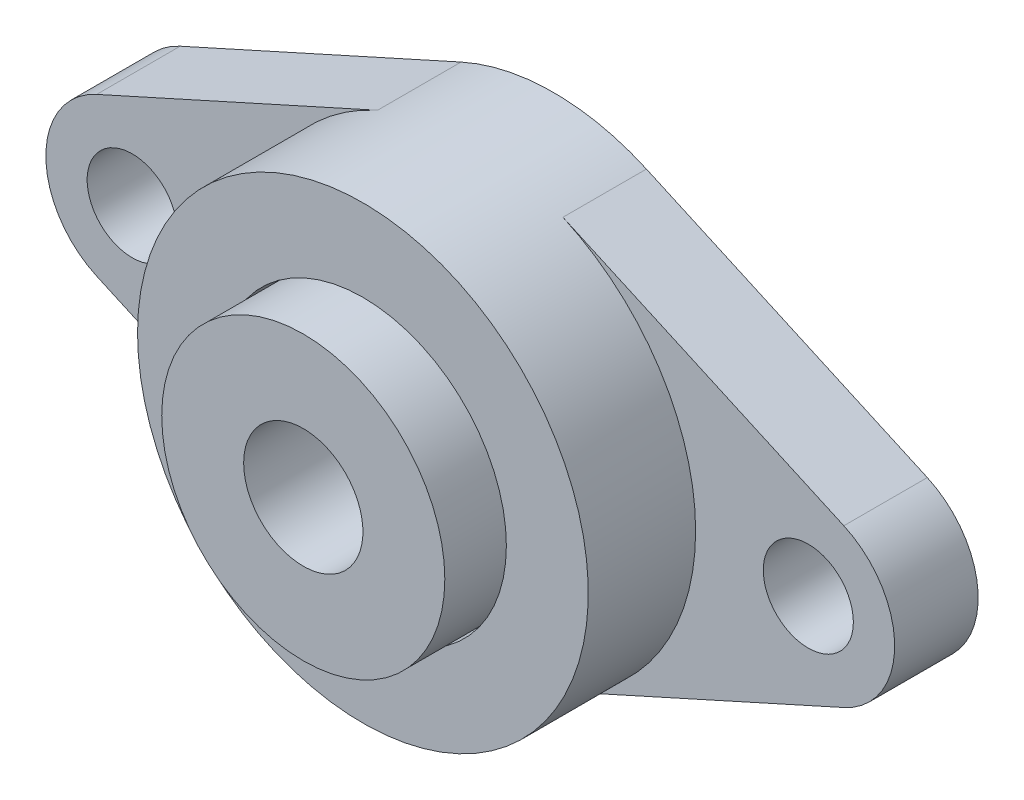
SolidWorks part; units mm, degrees
material "Cast Alloy Steel"
ref_plane "Front" through (0, 0, 0) normal (0, 0, 1) x (1, 0, 0)
ref_plane "Top" through (0, 0, 0) normal (0, 1, 0) x (1, 0, 0)
ref_plane "Right" through (0, 0, 0) normal (1, 0, 0) x (0, 0, -1)
sketch "Sketch1" plane through (0, 0, 0) normal (0, 0, 1) x (1, 0, 0)
  line L0 (-44.9961, 0) -> (44.9961, 0) construction
  line L1 (-49.7226, 10.4767) -> (-12.3359, 27.3435) construction
  line L2 (12.3359, 27.3435) -> (49.7226, 10.4767) construction
  line L3 (49.7226, -10.4767) -> (12.3359, -27.3435) construction
  line L4 (-12.3359, -27.3435) -> (-49.7226, -10.4767) construction
  line L5 (-44.9961, 11.4935) -> (-27.7082, 11.4935)
  line L6 (-44.9961, -11.4935) -> (-27.7082, -11.4935)
  line L7 (44.9961, 11.4935) -> (27.7082, 11.4935)
  line L8 (44.9961, -11.4935) -> (27.7082, -11.4935)
  circle A0 centre (-44.9961, 0) radius 5.9944
  circle A1 centre (44.9961, 0) radius 5.9944
  arc A2 (-44.9961, 11.4935) -> (-44.9961, -11.4935) centre (-44.9961, 0) ccw
  arc A3 (44.9961, -11.4935) -> (44.9961, 11.4935) centre (44.9961, 0) ccw
  circle A4 centre (0, 0) radius 29.9974 construction
  arc A5 (-27.7082, 11.4935) -> (-27.7082, -11.4935) centre (0, 0) ccw
  arc A6 (27.7082, 11.4935) -> (27.7082, -11.4935) centre (0, 0) cw
  dimension "F Bolt Size" = 11.9888
  dimension "Overall Width" = 59.9948
  dimension "E Ctr-to-Ctr" = 89.9922
  dimension "B Overall Length" = 112.9792
extrude "Extrude1" add sketch "Sketch1" along normal blind 11.1125
sketch "Sketch2" plane through (0, 0, 0) normal (0, 0, 1) x (1, 0, 0)
  line L0 (-49.7226, 10.4767) -> (-12.3359, 27.3435) construction
  line L1 (-44.9961, 11.4935) -> (-27.7082, 11.4935) construction
  line L2 (-44.9961, -11.4935) -> (-27.7082, -11.4935) construction
  line L3 (-12.3359, -27.3435) -> (-49.7226, -10.4767) construction
  line L4 (-49.7226, 10.4767) -> (-12.3359, 27.3435)
  line L5 (-44.9961, 11.4935) -> (-27.7082, 11.4935)
  line L6 (-44.9961, -11.4935) -> (-27.7082, -11.4935)
  line L7 (-12.3359, -27.3435) -> (-49.7226, -10.4767)
  line L8 (12.3359, 27.3435) -> (49.7226, 10.4767) construction
  line L9 (44.9961, 11.4935) -> (27.7082, 11.4935) construction
  line L10 (49.7226, -10.4767) -> (12.3359, -27.3435) construction
  line L11 (44.9961, -11.4935) -> (27.7082, -11.4935) construction
  line L12 (12.3359, 27.3435) -> (49.7226, 10.4767)
  line L13 (44.9961, 11.4935) -> (27.7082, 11.4935)
  line L14 (49.7226, -10.4767) -> (12.3359, -27.3435)
  line L15 (44.9961, -11.4935) -> (27.7082, -11.4935)
  circle A0 centre (0, 0) radius 29.9974 construction
  arc A1 (-44.9961, 11.4935) -> (-44.9961, -11.4935) centre (-44.9961, 0) ccw construction
  arc A2 (-12.3359, 27.3435) -> (-27.7082, 11.4935) centre (0, 0) ccw
  arc A3 (-44.9961, 11.4935) -> (-49.7226, 10.4767) centre (-44.9961, 0) ccw
  arc A4 (44.9961, -11.4935) -> (44.9961, 11.4935) centre (44.9961, 0) ccw construction
  arc A5 (44.9961, -11.4935) -> (49.7226, -10.4767) centre (44.9961, 0) ccw
  arc A6 (27.7082, 11.4935) -> (12.3359, 27.3435) centre (0, 0) ccw
  arc A7 (49.7226, 10.4767) -> (44.9961, 11.4935) centre (44.9961, 0) ccw
  arc A8 (-27.7082, -11.4935) -> (-12.3359, -27.3435) centre (0, 0) ccw
  arc A9 (12.3359, -27.3435) -> (27.7082, -11.4935) centre (0, 0) ccw
  arc A10 (-49.7226, -10.4767) -> (-44.9961, -11.4935) centre (-44.9961, 0) ccw
extrude "Extrude2" add sketch "Sketch2" along normal blind 11.1125
sketch "Sketch3" plane through (0, 0, 0) normal (1, 0, 0) x (0, 0, -1)
  line L0 (0, 29.9974) -> (-25.4, 29.9974)
  line L1 (0, 0) -> (-33.3375, 0) construction
  line L2 (0, 29.9974) -> (0, -29.9974) construction
  line L3 (-25.4, 29.9974) -> (-25.4, 19.0944)
  line L4 (-25.4, 19.0944) -> (-15.016, 19.0944)
  line L5 (0, 19.0944) -> (0, 29.9974)
  line L6 (-33.3375, 18.8404) -> (-15.016, 18.8404)
  line L7 (-33.3375, 18.8404) -> (-33.3375, 7.9375)
  line L8 (-33.3375, 7.9375) -> (-1.5875, 7.9375)
  line L9 (-1.5875, 18.8404) -> (-1.5875, 7.9375)
  line L10 (-33.3375, 0) -> (-33.3375, 7.9375) construction
  line L12 (-10.3187, 18.9674) -> (-10.3187, 19.0944) construction
  line L13 (-10.3187, 18.9674) -> (-10.3187, 18.8404) construction
  line L14 (-5.7468, 18.9674) -> (-5.6197, 18.9674) construction
  line L15 (-15.016, 19.0944) -> (-5.6215, 19.0944) construction
  line L16 (-5.6215, 19.0944) -> (0, 19.0944)
  line L17 (-5.6215, 18.8404) -> (-1.5875, 18.8404)
  line L18 (-15.016, 18.8404) -> (-5.6215, 18.8404) construction
  circle A0 centre (-10.3187, 18.9674) radius 4.572 construction
  arc A1 (-15.016, 18.8404) -> (-5.6215, 18.8404) centre (-10.3187, 18.9674) ccw
  arc A2 (-5.6215, 19.0944) -> (-15.016, 19.0944) centre (-10.3187, 18.9674) ccw
  arc A3 (-5.6215, 18.8404) -> (-5.6215, 19.0944) centre (-10.3187, 18.9674) ccw construction
  dimension "D3" = 9.144
  dimension "Body Height" = 25.4
  dimension "Shaft Dia" = 15.875
  dimension "C Overall Height" = 33.3375
  dimension "Bearing Back Space" = 1.5875
  dimension "Ball Location" = 10.3187
  dimension "D1" = 0.254
  dimension "D2" = 10.9029
  dimension "D4" = 0.127
  dimension "D5" = 18.3215
revolve "Revolve1" add sketch "Sketch3" angle 360 about L1
equation "\"D1@Extrude2\"=\"G Flange Thickness@Extrude1\""
equation "\"D1@Fillet2\"=\"G Flange Thickness@Extrude1\"/8"
equation "\"D1@Chamfer2\"=\"D5@Sketch3\"*.8"
equation "\"D7@Sketch6\"=\"Overall Width@Sketch1\"-.06"
equation "\"D1@Sketch7\"=\"Screw Size@Sketch7\"*.750"
equation "\"D1@Sketch9\"=\"Screw Size@Sketch7\"/2"
equation "\"D1@Cut-Extrude2\"=\"D1@Sketch9\"*.750"
